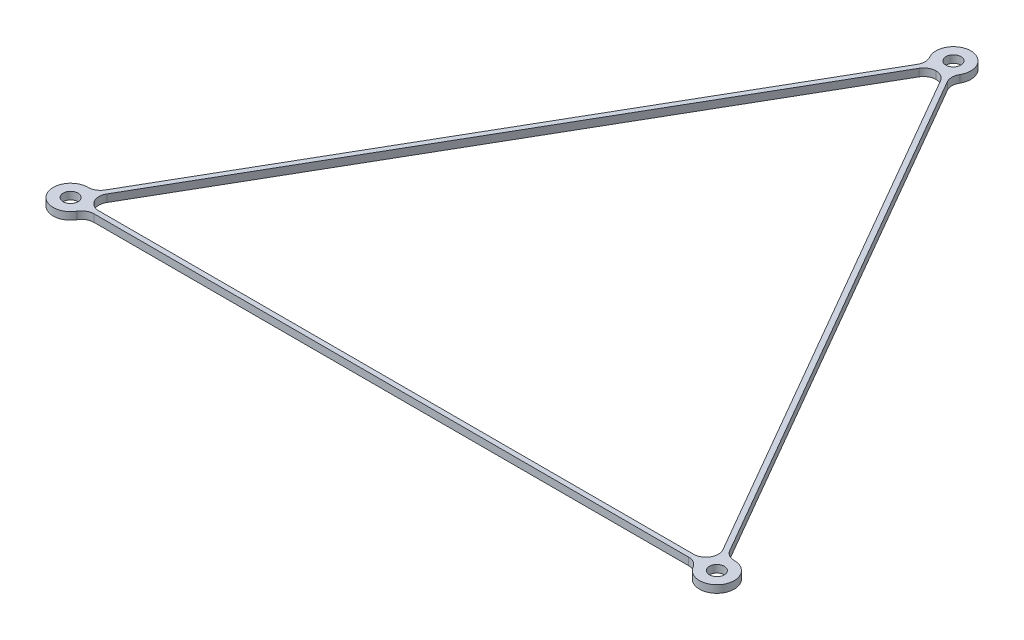
SolidWorks part; units mm, degrees
other "Markup1"
sketch "Sketch1" plane through (0, 0, 0) normal (0.4, 0.515, 0.7581) x (0.8844, 0, -0.4667)
ref_plane "Front Plane" through (0, 0, 0) normal (0, 0, 1) x (1, 0, 0)
ref_plane "Top Plane" through (0, 0, 0) normal (0, 1, 0) x (1, 0, 0)
ref_plane "Right Plane" through (0, 0, 0) normal (1, 0, 0) x (0, 0, -1)
sketch "Sketch2" plane through (0, 0, 0) normal (0, 1, 0) x (1, 0, 0)
  line L0 (65, -37.5278) -> (0, 0) construction
  line L1 (0, 0) -> (0, 75.0555) construction
  line L2 (0, 0) -> (-65, -37.5278) construction
  line L3 (65, -37.5278) -> (-65, -37.5278) construction
  line L4 (-65, -37.5278) -> (0, 75.0555) construction
  line L5 (0, 75.0555) -> (65, -37.5278) construction
  line L6 (-63.701, -34.2778) -> (-2.1651, 72.3055)
  line L7 (63.701, -34.2778) -> (2.1651, 72.3055)
  line L8 (61.5359, -38.0278) -> (-61.5359, -38.0278)
  line L9 (-61.5359, -37.0278) -> (61.5359, -37.0278)
  line L10 (62.8349, -34.7778) -> (1.299, 71.8055)
  line L11 (-1.299, 71.8055) -> (-62.8349, -34.7778)
  line L12 (-32.933, 19.0139) -> (-32.067, 18.5139) construction
  line L13 (0, -38.0278) -> (0, -37.0278) construction
  line L14 (32.933, 19.0139) -> (32.067, 18.5139) construction
  circle A0 centre (0, 75.0555) radius 1.5
  circle A1 centre (65, -37.5278) radius 1.5
  circle A2 centre (-65, -37.5278) radius 1.5
  arc A3 (62.8349, -34.7778) -> (61.5359, -37.0278) centre (65, -37.5278) ccw
  arc A4 (-61.5359, -37.0278) -> (-62.8349, -34.7778) centre (-65, -37.5278) ccw
  arc A5 (2.1651, 72.3055) -> (-2.1651, 72.3055) centre (0, 75.0555) ccw
  arc A6 (61.5359, -38.0278) -> (63.701, -34.2778) centre (65, -37.5278) ccw
  arc A7 (-63.701, -34.2778) -> (-61.5359, -38.0278) centre (-65, -37.5278) ccw
  arc A8 (-1.299, 71.8055) -> (1.299, 71.8055) centre (0, 75.0555) ccw
  point P14 (32.5, 18.7639)
  point P21 (-32.5, 18.7639)
  point P23 (0, -37.5278)
  dimension "D2" = 3
  dimension "D3" = 2
  dimension "D1" = 130
  dimension "D4" = 1
extrude "main_shape" add sketch "Sketch2" along normal mid plane 1.5
fillet "outside_fillet" radius 2.5 6 edges at (-2.1651, 0, -72.3055) (2.1651, 0, -72.3055) (63.701, 0, 34.2778) (61.5359, 0, 38.0278) (-61.5359, 0, 38.0278) (-63.701, 0, 34.2778)
fillet "inside_fillet" radius 2.5 6 edges at (-62.8349, 0, 34.7778) (-61.5359, 0, 37.0278) (61.5359, 0, 37.0278) (62.8349, 0, 34.7778) (1.299, 0, -71.8055) (-1.299, 0, -71.8055)
